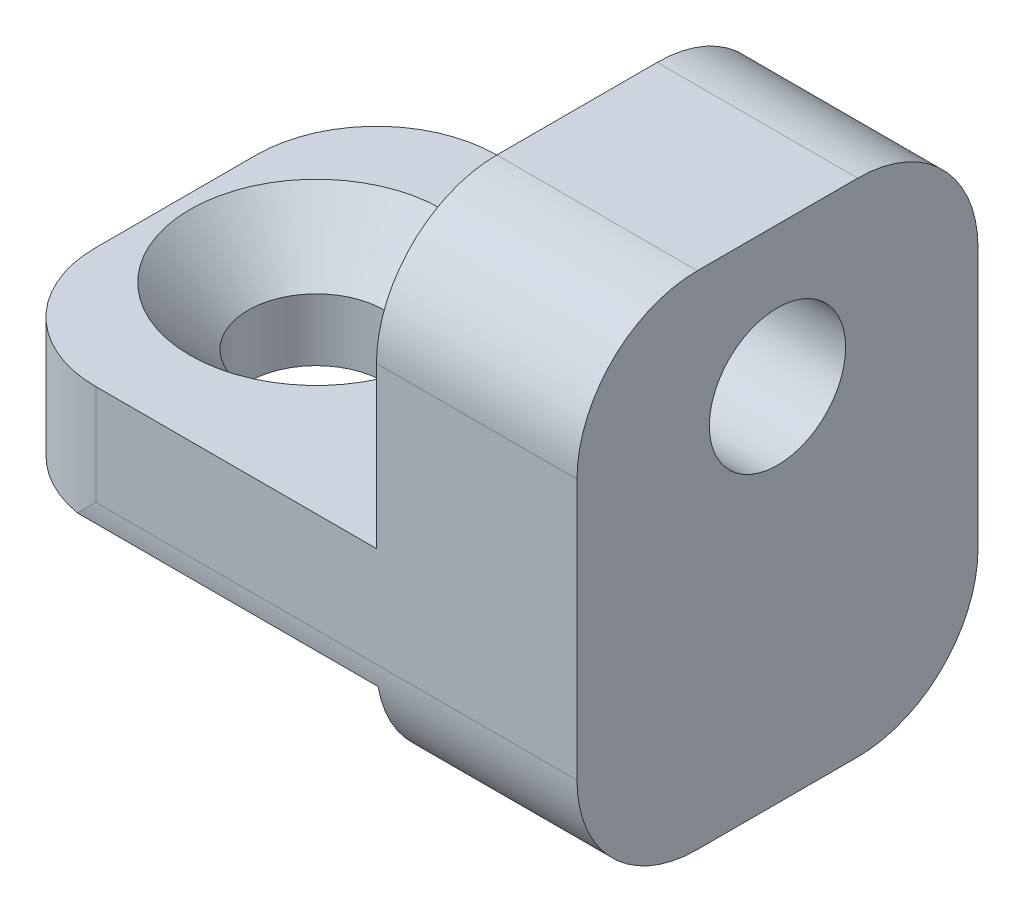
SolidWorks part; units mm, degrees
ref_plane "Plan de face" through (0, 0, 0) normal (0, 0, 1) x (1, 0, 0)
ref_plane "Plan de dessus" through (0, 0, 0) normal (0, 1, 0) x (1, 0, 0)
ref_plane "Plan de droite" through (0, 0, 0) normal (1, 0, 0) x (0, 0, -1)
sketch "Esquisse1" plane through (0, 0, 0) normal (0, 0, 1) x (1, 0, 0)
  line L1 (0, 0) -> (15, 0) construction
  line L2 (0, 0) -> (0, 10) construction
  line L3 (0, 10) -> (15, 10) construction
  line L4 (15, 0) -> (15, 10) construction
  line L5 (15, 0) -> (15, 10)
  line L6 (15, 10) -> (10, 10)
  line L7 (10, 10) -> (10, 3)
  line L8 (10, 3) -> (0, 3)
  line L9 (0, 3) -> (0, 0)
  line L10 (0, 0) -> (10, 0)
  line L11 (10, 0) -> (10, -2.5)
  line L12 (10, -2.5) -> (15, -2.5)
  line L13 (15, -2.5) -> (15, 0)
  dimension "D1" = 15
  dimension "D2" = 10
  dimension "D3" = 5
  dimension "D4" = 3
  dimension "D5" = 2.5
  dimension "D6" = 5
extrude "Boss.-Extru.1" add sketch "Esquisse1" along normal blind 10
sketch "Esquisse2" plane through (15, 0, 0) normal (1, 0, 0) x (0, 0, -1)
  line L0 (-10, 10) -> (0, 10) construction
  line L1 (-10, -2.5) -> (-10, 10) construction
  circle A0 centre (-5, 6.5) radius 1.5
  dimension "D2" = 3
  dimension "D1" = 3.5
  dimension "D3" = 5
extrude "Enlèv. mat.-Extru.1" cut sketch "Esquisse2" against normal up to surface (5 mm away) up to face at (10, 6.5, 5)
sketch "Esquisse3" plane through (0, 3, 0) normal (0, 1, 0) x (1, 0, 0)
  line L0 (0, -10) -> (0, 0) construction
  line L1 (10, -10) -> (0, -10) construction
  circle A0 centre (3.5, -5) radius 1.5
  dimension "D2" = 3
  dimension "D1" = 3.5
  dimension "D3" = 5
extrude "Enlèv. mat.-Extru.2" cut sketch "Esquisse3" against normal up to surface (3 mm away) up to face at (5, 0, 5)
hole_wizard "Dégagement M31" positions "Esquisse4" profile "Esquisse5" hole size "M3" standard "ISO"
sketch "Esquisse4" plane through (15, 0, 0) normal (1, 0, 0) x (0, 0, -1)
  point P0 (-5, 6.5)
sketch "Esquisse5" plane through (15, 6.5, 5) normal (0, 1, 0) x (0, 0, -1)
  line L0 (0, 0) -> (0, 6.0215)
  line L1 (0, 6.0215) -> (1.7, 5)
  line L2 (1.7, 5) -> (1.7, 0)
  line L5 (1.7, 0) -> (0, 0)
  line L10 (0, 6.0215) -> (-1.7, 5) construction
  line L11 (0, -6.35) -> (0, 107.95) construction
  dimension "Diamètre du perçage" = 3.4
  dimension "Profondeur du perçage" = 5
  dimension "Angle de pointe" = 118
hole_wizard "Fraisage pour vis à tête fraisée M31" positions "Esquisse6" profile "Esquisse7" countersink size "M3" standard "ISO"
sketch "Esquisse6" plane through (0, 3, 0) normal (0, 1, 0) x (1, 0, 0)
  point P0 (3.5, -5)
sketch "Esquisse7" plane through (3.5, 3, 5) normal (1, 0, 0) x (0, 0, 1)
  line L0 (0, 0) -> (0, 4.0215)
  line L1 (0, 4.0215) -> (1.7, 3)
  line L2 (1.7, 3) -> (1.7, 1.45)
  line L3 (1.7, 1.45) -> (3.15, 0)
  line L5 (3.15, 0) -> (0, 0)
  line L6 (-1.7, 1.45) -> (-3.15, 0) construction
  line L10 (0, 4.0215) -> (-1.7, 3) construction
  line L11 (0, -6.35) -> (0, 107.95) construction
  dimension "Diamètre du perçage" = 3.4
  dimension "Profondeur du perçage" = 3
  dimension "Diamètre du fraisage entrant" = 6.3
  dimension "Angle du fraisage entrant" = 90
  dimension "Angle de pointe" = 118
fillet "Congé1" radius 3 6 edges at (0, 1.5, 10) (0, 1.5, 0) (12.5, 10, 0) (12.5, 10, 10) (12.5, -2.5, 0) (12.5, -2.5, 10)
